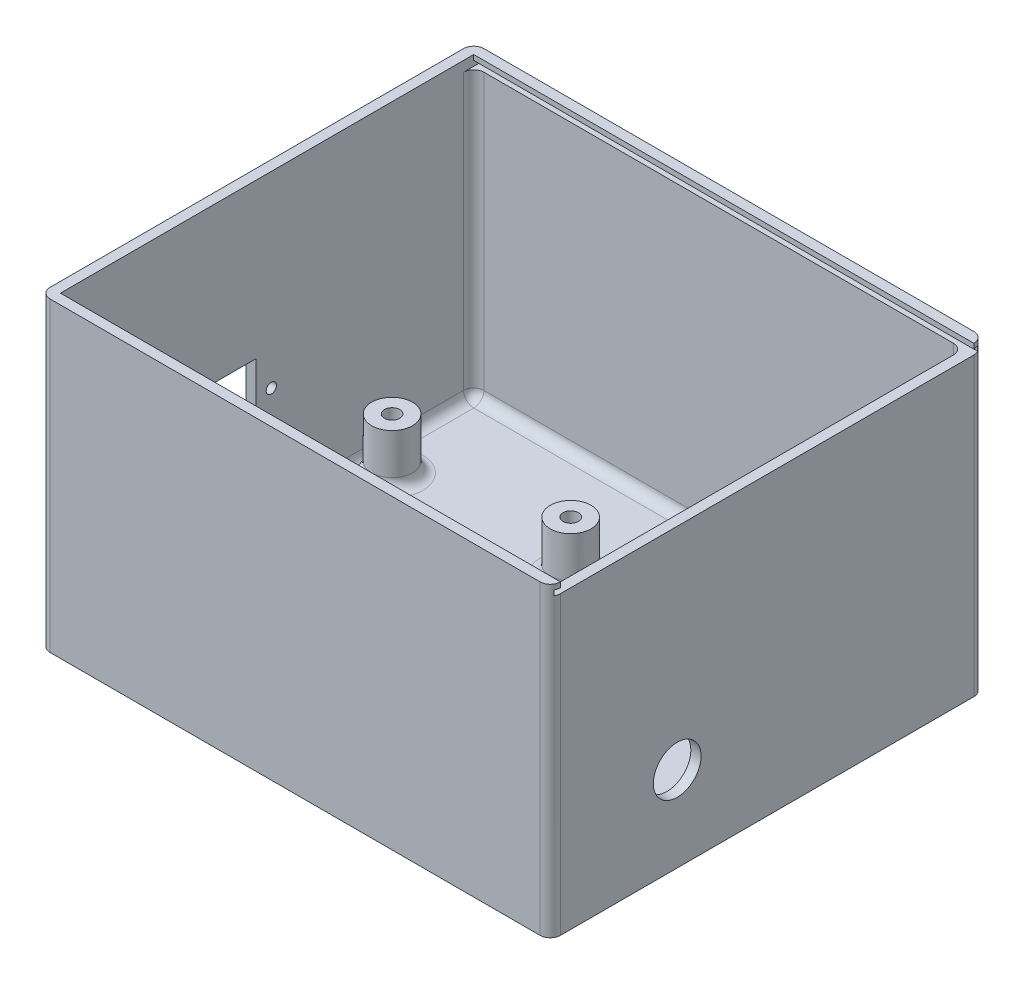
SolidWorks part; units mm, degrees
ref_plane "Front Plane" through (0, 0, 0) normal (0, 0, 1) x (1, 0, 0)
ref_plane "Top Plane" through (0, 0, 0) normal (0, 1, 0) x (1, 0, 0)
ref_plane "Right Plane" through (0, 0, 0) normal (1, 0, 0) x (0, 0, -1)
sketch "Sketch2" plane through (0, 0, 0) normal (0, 1, 0) x (1, 0, 0)
  line L1 (0, 0) -> (100, 0)
  line L2 (0, 0) -> (0, 85)
  line L3 (0, 85) -> (100, 85)
  line L4 (100, 0) -> (100, 85)
  dimension "D1" = 100
  dimension "D2" = 85
extrude "Boss-Extrude1" add sketch "Sketch2" along normal blind 60
shell "Shell1" thickness 2 removed face at (50, 60, -42.5)
sketch "Sketch3" plane through (0, 2, 0) normal (0, 1, 0) x (1, 0, 0)
  line L5 (2, 2) -> (98, 2) construction
  circle A0 centre (7, 62) radius 4
  circle A1 centre (7, 12) radius 4
  circle A2 centre (42, 12) radius 4
  circle A3 centre (42, 62) radius 4
  circle A4 centre (71, 7) radius 4
  circle A5 centre (71, 77) radius 4
  circle A6 centre (7, 62) radius 1.5
  circle A7 centre (42, 62) radius 1.5
  circle A8 centre (42, 12) radius 1.5
  circle A9 centre (7, 12) radius 1.5
  circle A10 centre (71, 7) radius 1.5
  circle A11 centre (71, 77) radius 1.5
  dimension "D1" = 8
  dimension "D2" = 8
  dimension "D3" = 8
  dimension "D4" = 8
  dimension "D9" = 8
  dimension "D10" = 8
  dimension "D14" = 3
  dimension "D15" = 3
  dimension "D16" = 3
  dimension "D17" = 3
  dimension "D18" = 3
  dimension "D19" = 3
  dimension "D5" = 50
  dimension "D6" = 35
  dimension "D11" = 70
  dimension "D12" = 5
extrude "Boss-Extrude2" add sketch "Sketch3" along normal blind 10
sketch "Sketch4" plane through (0, 0, 0) normal (-1, 0, 0) x (0, 0, 1)
  line L1 (-40.3319, 29.7127) -> (-20.3319, 29.7127)
  line L2 (-40.3319, 29.7127) -> (-40.3319, 16.7127)
  line L3 (-40.3319, 16.7127) -> (-20.3319, 16.7127)
  line L4 (-20.3319, 29.7127) -> (-20.3319, 16.7127)
  circle A0 centre (-43.3319, 23.2127) radius 1
  circle A1 centre (-17.3319, 23.2127) radius 1
  dimension "D3" = 2
  dimension "D4" = 2
  dimension "D1" = 20
  dimension "D2" = 13
  dimension "D5" = 26
  dimension "D6" = 3
extrude "Cut-Extrude1" cut sketch "Sketch4" against normal blind 10
sketch "Sketch5" plane through (100, 0, 0) normal (1, 0, 0) x (0, 0, -1)
  circle A0 centre (24.8733, 16.6647) radius 4.6751
extrude "Cut-Extrude2" cut sketch "Sketch5" against normal blind 10
sketch "Sketch6" plane through (100, 0, 0) normal (1, 0, 0) x (0, 0, -1)
  line L0 (0, 60) -> (85, 60) construction
  line L1 (83, 60) -> (2, 60)
  line L2 (83, 60) -> (83, 58)
  line L3 (83, 58) -> (2, 58)
  line L4 (2, 60) -> (2, 58)
  line L5 (85, 60) -> (85, 0) construction
  line L6 (0, 60) -> (0, 0) construction
  dimension "D1" = 2
  dimension "D2" = 2
  dimension "D3" = 2
extrude "Cut-Extrude3" cut sketch "Sketch6" against normal blind 10
sketch "Sketch7" plane through (0, 0, -83) normal (0, 0, 1) x (1, 0, 0)
  line L0 (2, 60) -> (2, 2) construction
  line L1 (100, 58) -> (2, 58)
  line L2 (100, 58) -> (100, 59)
  line L3 (100, 59) -> (2, 59)
  line L4 (2, 58) -> (2, 59)
  dimension "D1" = 1
extrude "Cut-Extrude4" cut sketch "Sketch7" against normal blind 1
sketch "Sketch8" plane through (0, 0, -2) normal (0, 0, -1) x (-1, 0, 0)
  line L0 (-2, 60) -> (-2, 2) construction
  line L1 (-100, 58) -> (-2, 58)
  line L2 (-100, 58) -> (-100, 59)
  line L3 (-100, 59) -> (-2, 59)
  line L4 (-2, 58) -> (-2, 59)
  dimension "D1" = 1
extrude "Cut-Extrude5" cut sketch "Sketch8" against normal blind 1
fillet "Fillet1" radius 2 18 edges at (7, 2, -66) (7, 2, -16) (71, 2, -81) (42, 2, -66) (42, 2, -16) (71, 2, -11) (50, 2, -2) (98, 2, -42.5) (2, 2, -42.5) (50, 2, -83) (2, 30, -83) (98, 30, -83) (98, 30, -2) (2, 30, -2) (100, 30, 0) (100, 30, -85) (0, 30, -85) (0, 30, 0)
